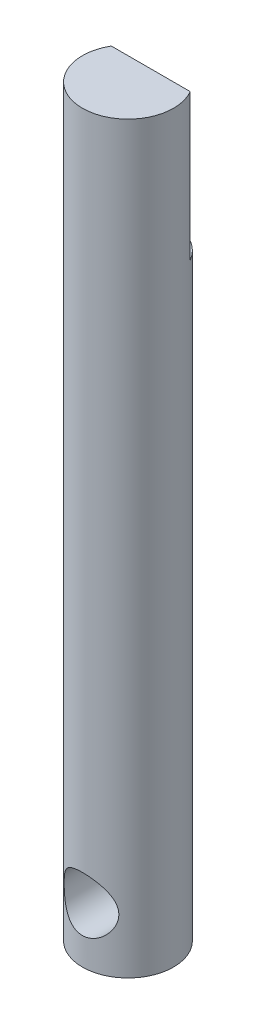
SolidWorks part; units mm, degrees
material "Plain Carbon Steel"
ref_plane "Front Plane" through (0, 0, 0) normal (0, 0, 1) x (1, 0, 0)
ref_plane "Top Plane" through (0, 0, 0) normal (0, 1, 0) x (1, 0, 0)
ref_plane "Right Plane" through (0, 0, 0) normal (1, 0, 0) x (0, 0, -1)
sketch "Sketch1" plane through (0, 0, 0) normal (0, 1, 0) x (1, 0, 0)
  circle A0 centre (0, 0) radius 3.9688
extrude "Boss-Extrude1" add sketch "Sketch1" along normal blind 64.77
sketch "Sketch2" plane through (0, 64.77, 0) normal (0, 1, 0) x (1, 0, 0)
  line L0 (0, 0) -> (3.437, 1.9844) construction
  line L1 (3.437, 1.9844) -> (-3.437, 1.9844)
  line L2 (-3.437, 1.9844) -> (0, 0) construction
  line L3 (-3.437, 1.9844) -> (-4.7194, 2.5225)
  line L4 (-4.7194, 2.5225) -> (-2.5902, 6.3532)
  line L5 (-2.5902, 6.3532) -> (2.4567, 4.7289)
  line L6 (2.4567, 4.7289) -> (3.437, 1.9844)
  circle A1 centre (0, 0) radius 3.9688 construction
  point P2 (0, 1.9844)
  dimension "D1" = 120
extrude "Cut-Extrude1" cut sketch "Sketch2" against normal blind 12.7
sketch "Sketch3" plane through (0, 0, -1.9844) normal (0, 0, -1) x (-1, 0, 0)
  line L0 (0, 0) -> (0, 9.525) construction
  circle A0 centre (0, 4.7625) radius 2.3813
  dimension "D2" = 4.7625
  dimension "D1" = 9.525
extrude "Cut-Extrude2" cut sketch "Sketch3" against normal blind 12.7 and the other way blind 12.7
